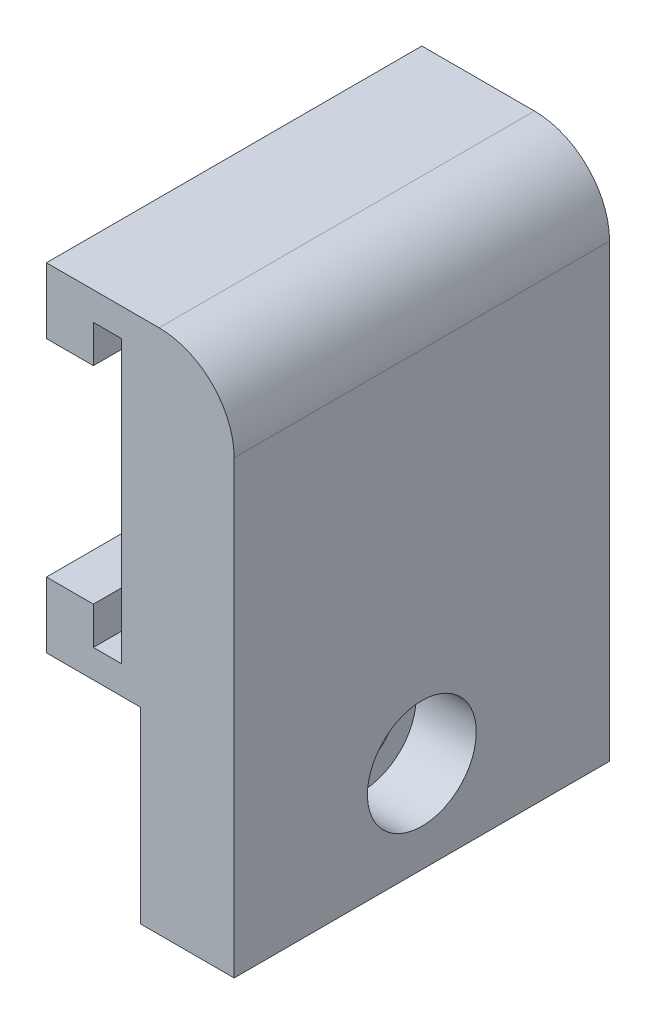
SolidWorks part; units mm, degrees
ref_plane "Front Plane" through (0, 0, 0) normal (0, 0, 1) x (1, 0, 0)
ref_plane "Top Plane" through (0, 0, 0) normal (0, 1, 0) x (1, 0, 0)
ref_plane "Right Plane" through (0, 0, 0) normal (1, 0, 0) x (0, 0, -1)
sketch "Profile" plane through (0, 0, 0) normal (0, 0, 1) x (1, 0, 0)
  line L1 (-6.35, 22.86) -> (6.35, 22.86)
  line L2 (-6.35, 22.86) -> (-6.35, 0)
  line L3 (-6.35, 0) -> (6.35, 0)
  line L4 (6.35, 22.86) -> (6.35, 0)
  line L5 (0, 0) -> (6.35, 0)
  line L6 (0, 0) -> (0, -12.7)
  line L7 (0, -12.7) -> (6.35, -12.7)
  line L8 (6.35, 0) -> (6.35, -12.7)
  dimension "D1" = 22.86
  dimension "D2" = 12.7
  dimension "D3" = 6.35
  dimension "D4" = 12.7
extrude "Boss-Extrude1" add sketch "Profile" along normal mid plane 25.4 contours L4 L1 L2 L3 | L8 L3 L6 L7 region at (0, 11.43, 0) region at (3.175, -6.35, 0)
sketch "ScrewHole" plane through (0, 0, 0) normal (-1, 0, 0) x (0, 0, 1)
  line L2 (12.7, 0) -> (-12.7, 0) construction
  circle A0 centre (0, -6.477) radius 2.159
  dimension "D1" = 4.318
  dimension "D2" = 6.477
extrude "Cut-Extrude1" cut sketch "ScrewHole" against normal through all both
sketch "Sketch3" plane through (6.35, 0, 0) normal (1, 0, 0) x (0, 0, -1)
  circle A0 centre (0, -6.477) radius 2.159 construction
  circle A1 centre (0, -6.477) radius 2.159
  circle A2 centre (0, -6.477) radius 3.683
  dimension "D1" = 7.366
extrude "Cut-Extrude2" cut sketch "Sketch3" against normal blind 4.064
sketch "Sketch6" plane through (0, 0, -12.7) normal (0, 0, -1) x (-1, 0, 0)
  line L0 (6.35, 22.86) -> (6.35, 0) construction
  line L1 (1.27, 20.955) -> (3.175, 20.955)
  line L2 (1.27, 20.955) -> (1.27, 1.905)
  line L3 (1.27, 1.905) -> (3.175, 1.905)
  line L4 (3.175, 20.955) -> (3.175, 18.415)
  line L5 (3.175, 18.415) -> (6.35, 18.415)
  line L6 (3.175, 18.415) -> (3.175, 4.445) construction
  line L7 (3.175, 4.445) -> (6.35, 4.445)
  line L8 (6.35, 18.415) -> (6.35, 4.445) construction
  line L9 (3.175, 18.415) -> (3.175, 4.445) construction
  line L10 (3.175, 4.445) -> (3.175, 1.905)
  line L12 (6.35, 18.415) -> (7.62, 18.415)
  line L13 (6.35, 18.415) -> (6.35, 4.445) construction
  line L14 (6.35, 4.445) -> (7.62, 4.445)
  line L15 (7.62, 18.415) -> (7.62, 4.445)
  point P8 (1.27, 11.43)
  point P12 (6.35, 11.43)
  point P18 (6.35, 11.43)
  dimension "D1" = 1.905
  dimension "D2" = 19.05
  dimension "D3" = 13.97
  dimension "D4" = 3.175
  dimension "D5" = 1.27
extrude "Cut-Extrude3" cut sketch "Sketch6" against normal through all both
fillet "Fillet3" radius 5.08 1 edges at (6.35, 22.86, 0)
